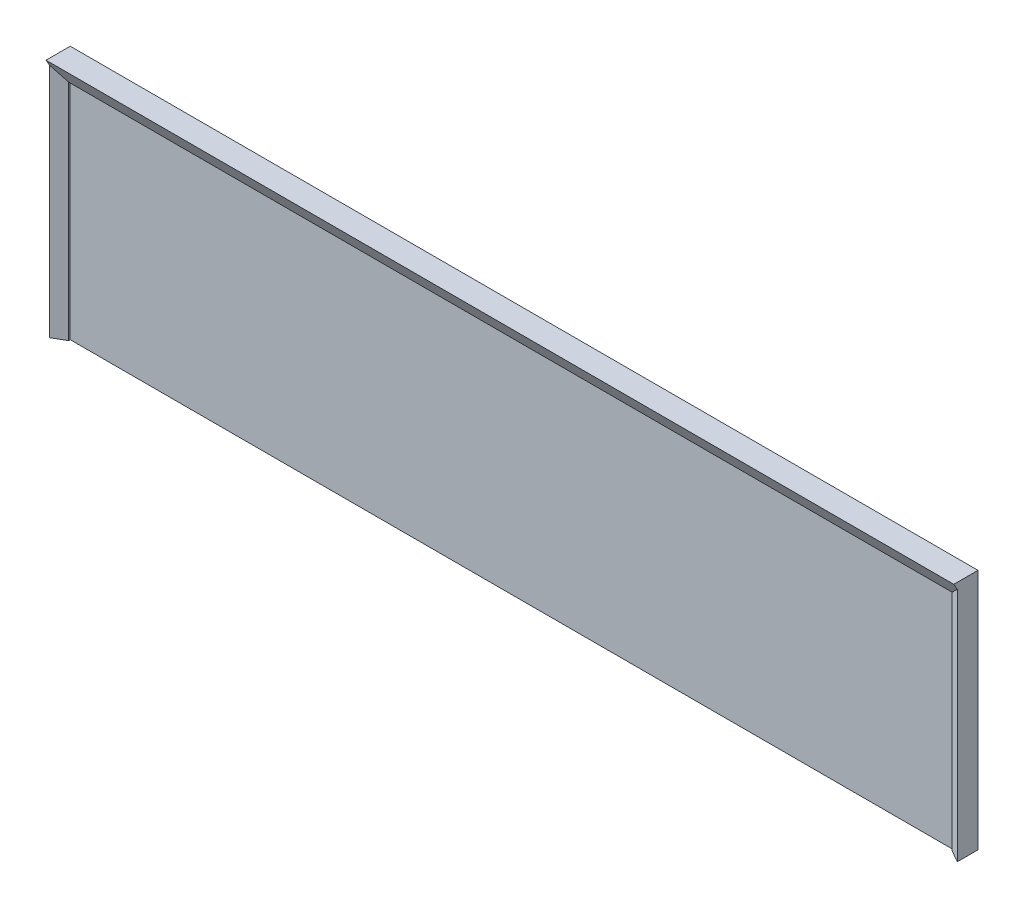
SolidWorks part; units mm, degrees
ref_plane "Front Plane" through (0, 0, 0) normal (0, 0, 1) x (1, 0, 0)
ref_plane "Top Plane" through (0, 0, 0) normal (0, 1, 0) x (1, 0, 0)
ref_plane "Right Plane" through (0, 0, 0) normal (1, 0, 0) x (0, 0, -1)
sketch "Sketch1" plane through (0, 0, 0) normal (0, 0, 1) x (1, 0, 0)
  line L0 (2, 37) -> (2, 0)
  line L1 (0, 0) -> (150, 0)
  line L2 (0, 0) -> (0, 40)
  line L3 (0, 40) -> (150, 40)
  line L4 (150, 0) -> (150, 40)
  line L5 (148, 37) -> (148, 0)
  line L6 (2, 37) -> (148, 37)
  dimension "D1" = 150
  dimension "D2" = 40
  dimension "D3" = 2
  dimension "D4" = 2
  dimension "D5" = 3
extrude "Boss-Extrude1" add sketch "Sketch1" along normal blind 2 contours L6 L0 L1 L5 region at (75, 18.5, 0)
extrude "Boss-Extrude2" add sketch "Sketch1<4>" along normal blind 4 contours L0 L6 L5 L1 L4 L3 L2 region at (0.4476, 18.5, 0)
sketch "Sketch1<4>" plane through (0, 0, 0) normal (0, 0, 1) x (1, 0, 0) same geometry as "Sketch1"
chamfer "Chamfer1" distance 3 angle 30 3 edges at (148, 18.5, 4) (2, 18.5, 4) (75, 37, 4) first distance on face at (75, 19.25, 4)
